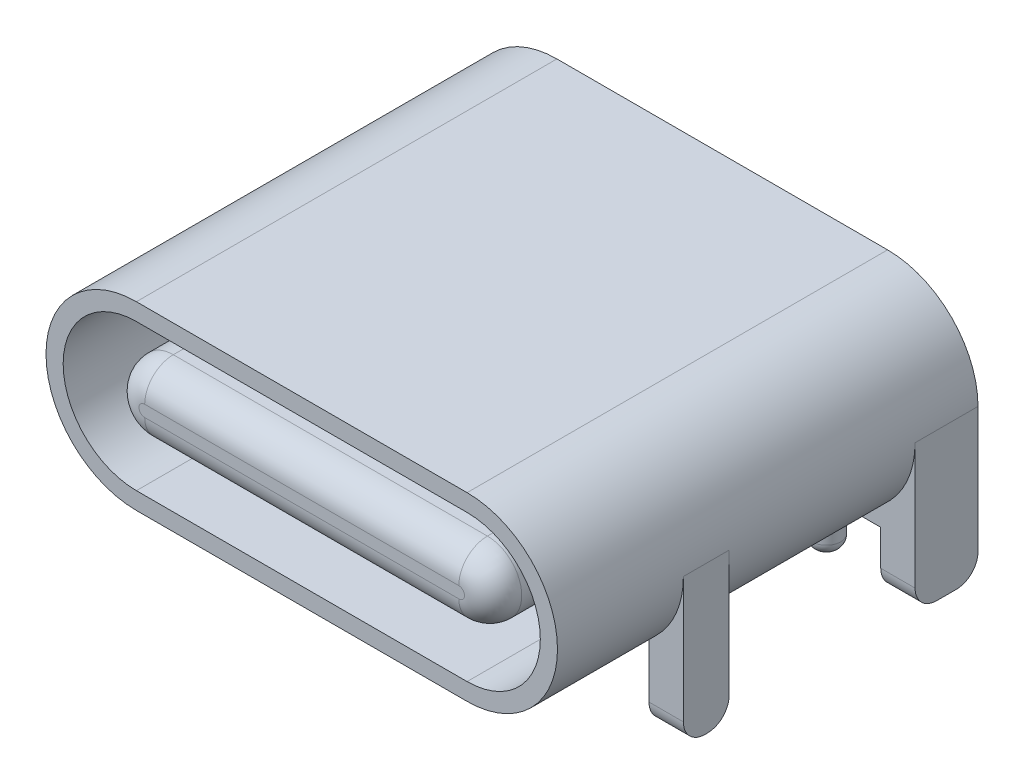
SolidWorks part; units mm, degrees
ref_plane "Front Plane" through (0, 0, 0) normal (0, 0, 1) x (1, 0, 0)
ref_plane "Top Plane" through (0, 0, 0) normal (0, 1, 0) x (1, 0, 0)
ref_plane "Right Plane" through (0, 0, 0) normal (1, 0, 0) x (0, 0, -1)
sketch "Sketch1" plane through (0, 0, 0) normal (0, 1, 0) x (1, 0, 0)
  line L1 (-4.47, 3.675) -> (4.47, 3.675)
  line L2 (-4.47, 3.675) -> (-4.47, -3.675)
  line L3 (-4.47, -3.675) -> (4.47, -3.675)
  line L4 (4.47, 3.675) -> (4.47, -3.675)
  line L5 (-4.47, 3.675) -> (4.47, -3.675) construction
  line L6 (-4.47, -3.675) -> (4.47, 3.675) construction
  point P0 (0, 0)
  point P5 (-1.9738, 5.526)
  dimension "D1" = 8.94
  dimension "D2" = 7.35
extrude "Boss-Extrude1" add sketch "Sketch1" along normal blind 3.16
sketch "Sketch2" plane through (0, 0, 3.675) normal (0, 0, 1) x (1, 0, 0)
  line L0 (0, 3.16) -> (0, 0) construction
  line L1 (-4.47, 3.16) -> (4.47, 3.16) construction
  line L2 (-2.89, 1.58) -> (-2.89, 3.16)
  line L7 (-4.47, 0) -> (4.47, 3.16) construction
  line L8 (-4.741, 1.58) -> (4.741, 1.58) construction
  line L9 (-2.89, 1.58) -> (-2.89, 0)
  line L10 (2.89, 1.58) -> (2.89, 3.16)
  line L11 (2.89, 1.58) -> (2.89, 0)
  line L12 (-2.89, 3.16) -> (2.89, 3.16)
  line L13 (-2.89, 0) -> (2.89, 0)
  line L15 (-3.345, 2.18) -> (3.345, 2.18)
  line L16 (-3.345, 2.18) -> (-3.345, 0.98)
  line L17 (-3.345, 0.98) -> (3.345, 0.98)
  line L18 (3.345, 2.18) -> (3.345, 0.98)
  line L19 (-3.345, 2.18) -> (3.345, 0.98) construction
  line L20 (-3.345, 0.98) -> (3.345, 2.18) construction
  line L21 (-4.47, 3.16) -> (4.47, 3.16)
  line L22 (-4.47, 3.16) -> (-4.47, 0)
  line L23 (-4.47, 0) -> (4.47, 0)
  line L24 (4.47, 3.16) -> (4.47, 0)
  line L25 (-4.47, 3.16) -> (4.47, 0) construction
  line L26 (-4.47, 0) -> (4.47, 3.16) construction
  circle A0 centre (-2.89, 1.58) radius 1.58
  circle A1 centre (2.89, 1.58) radius 1.58
  circle A2 centre (-2.745, 1.58) radius 0.6
  circle A3 centre (2.745, 1.58) radius 0.6
  point P5 (0, 1.58)
  point P10 (0, 1.58)
  point P24 (0, 1.58)
  line M12 (-4.47, 0) -> (4.47, 0)
  line M13 (4.47, 0) -> (4.47, 3.16)
  line M14 (4.47, 3.16) -> (-4.47, 3.16)
  line M15 (-4.47, 3.16) -> (-4.47, 0)
  dimension "D1" = 6.69
  dimension "D2" = 0
  dimension "D3" = 1.2
extrude "Cut-Extrude1" cut sketch "Sketch2" against normal blind 2.2 contours A0 M14 M15 | A0 L22 M12 | A1 M12 M13 | A1 L24 M14 region at (-4.1171, 2.8071, 3.675) region at (-4.1171, 0.3529, 3.675) region at (4.1171, 2.8071, 3.675) region at (4.1171, 0.3529, 3.675)
sketch "Sketch4" plane through (0, 0, 1.475) normal (0, 0, 1) x (1, 0, 0)
  line L1 (-4.47, 3.16) -> (4.47, 3.16)
  line L2 (-4.47, 3.16) -> (-4.47, 0)
  line L3 (-4.47, 0) -> (4.47, 0)
  line L4 (4.47, 3.16) -> (4.47, 0)
  line L5 (-4.47, 3.16) -> (4.47, 0) construction
  line L6 (-4.47, 0) -> (4.47, 3.16) construction
  circle A0 centre (-2.89, 1.58) radius 1.58
  circle A1 centre (2.89, 1.58) radius 1.58
  point P0 (0, 1.58)
  arc M1 (-4.47, 1.58) -> (-2.89, 3.16) centre (-2.89, 1.58) cw
  line M2 (-2.89, 3.16) -> (-4.47, 3.16)
  line M3 (-4.47, 3.16) -> (-4.47, 1.58)
extrude "Cut-Extrude2" cut sketch "Sketch4" against normal blind 0.8 contours M3 M1 M2 | A1 L4 L1 region at (-4.1171, 2.8071, 1.475) region at (4.1171, 2.8071, 1.475)
sketch "Sketch5" plane through (0, 0, -3.675) normal (0, 0, -1) x (-1, 0, 0)
  line L0 (0, 3.16) -> (0, 0) construction
  line L1 (-4.47, 3.16) -> (4.47, 3.16) construction
  line L3 (-4.47, 3.16) -> (4.47, 3.16)
  line L4 (-4.47, 3.16) -> (-4.47, 0)
  line L5 (-4.47, 0) -> (4.47, 0)
  line L6 (4.47, 3.16) -> (4.47, 0)
  line L7 (-4.47, 3.16) -> (4.47, 0) construction
  line L8 (-4.47, 0) -> (4.47, 3.16) construction
  circle A0 centre (-2.89, 1.58) radius 1.58
  circle A1 centre (2.89, 1.58) radius 1.58
  point P5 (0, 1.58)
  line M1 (-4.47, 0) -> (4.47, 0)
  line M2 (4.47, 0) -> (4.47, 3.16)
  line M3 (4.47, 3.16) -> (-4.47, 3.16)
  line M4 (-4.47, 3.16) -> (-4.47, 0)
extrude "Cut-Extrude3" cut sketch "Sketch5" against normal blind 3.25 from offset 1.1 contours A0 L3 M4 | A1 L6 M3 | A0 L4 M1 | A1 M1 M2 region at (4.1171, 2.8071, -3.675) region at (4.1171, 0.3529, -3.675) region at (-4.1171, 2.8071, -3.675) region at (-4.1171, 0.3529, -3.675) offset against normal yes
sketch "Sketch6" plane through (0, 0, -3.675) normal (0, 0, -1) x (-1, 0, 0)
  line L1 (-4.47, 3.16) -> (4.47, 3.16)
  line L2 (-4.47, 3.16) -> (-4.47, 0)
  line L3 (-4.47, 0) -> (4.47, 0)
  line L4 (4.47, 3.16) -> (4.47, 0)
  line L5 (-4.47, 3.16) -> (4.47, 0) construction
  line L6 (-4.47, 0) -> (4.47, 3.16) construction
  circle A0 centre (-2.89, 1.58) radius 1.58
  circle A1 centre (2.89, 1.58) radius 1.58
  point P0 (0, 1.58)
  line M3 (4.47, 3.16) -> (-4.47, 3.16)
  line M4 (-4.47, 3.16) -> (-4.47, 0)
extrude "Cut-Extrude4" cut sketch "Sketch6" against normal blind 3.25 contours A0 L1 M4 | A1 L4 M3 region at (4.1171, 2.8071, -3.675) region at (-4.1171, 2.8071, -3.675)
sketch "Sketch7" plane through (0, 0, 3.675) normal (0, 0, 1) x (1, 0, 0)
  line L0 (0, 3.16) -> (0, 0) construction
  line L1 (-2.89, 3.16) -> (2.89, 3.16) construction
  line L3 (-3.345, 2.18) -> (3.345, 2.18)
  line L4 (-3.345, 2.18) -> (-3.345, 0.98)
  line L5 (-3.345, 0.98) -> (3.345, 0.98)
  line L6 (3.345, 2.18) -> (3.345, 0.98)
  line L7 (-3.345, 2.18) -> (3.345, 0.98) construction
  line L8 (-3.345, 0.98) -> (3.345, 2.18) construction
  line L9 (-4.17, 2.86) -> (4.17, 2.86)
  line L10 (-4.17, 2.86) -> (-4.17, 0.3)
  line L11 (-4.17, 0.3) -> (4.17, 0.3)
  line L12 (4.17, 2.86) -> (4.17, 0.3)
  line L13 (-4.17, 2.86) -> (4.17, 0.3) construction
  line L14 (-4.17, 0.3) -> (4.17, 2.86) construction
  circle A0 centre (-2.745, 1.58) radius 0.6
  circle A1 centre (2.745, 1.58) radius 0.6
  circle A2 centre (-2.89, 1.58) radius 1.28
  circle A3 centre (2.89, 1.58) radius 1.28
  point P5 (0, 1.58)
  point P10 (0, 1.58)
  dimension "D1" = 6.69
  dimension "D2" = 1.2
  dimension "D3" = 8.34
  dimension "D4" = 2.56
extrude "Cut-Extrude5" cut sketch "Sketch7" against normal offset from surface (6.25 mm away) 1.1 contours L3 A2 L5 L4 | A0 L3 L4 | A0 L4 L5 | A1 L5 L6 | A3 L9 A2 L3 | A3 L5 A2 L11 | A1 L6 L3 | A3 L3 L6 L5 region at (-3.3802, 1.88, 3.675) region at (-3.211, 2.046, 3.675) region at (-3.211, 1.114, 3.675) region at (0, 2.5435, 3.675) region at (2.2484, 2.6468, 3.675) region at (0, 0.6165, 3.675) region at (3.211, 2.046, 3.675) region at (3.211, 1.114, 3.675) up to face at (0, 1.6891, -3.675)
fillet "Fillet1" radius 0.5 4 edges at (3.345, 1.58, 3.675) (0, 0.98, 3.675) (-3.345, 1.58, 3.675) (0, 2.18, 3.675)
sketch "Sketch8" plane through (0, 0, 1.475) normal (0, 0, 1) x (1, 0, 0)
  line L2 (-4.47, 0) -> (4.47, 0)
  line L3 (-4.47, 0) -> (-4.47, 1.58)
  line L4 (-4.47, 1.58) -> (4.47, 1.58)
  line L5 (4.47, 0) -> (4.47, 1.58)
  line L6 (-4.47, 1.58) -> (4.47, 1.58)
  line L7 (-4.47, 1.58) -> (-4.47, 3.16)
  line L8 (-4.47, 3.16) -> (4.47, 3.16)
  line L9 (4.47, 1.58) -> (4.47, 3.16)
  line L10 (-4.47, 0) -> (-3.87, 0)
  line L11 (-4.47, 0) -> (-4.47, 1.58)
  line L12 (-4.47, 1.58) -> (-3.87, 1.58)
  line L13 (-3.87, 0) -> (-3.87, 1.58)
  line L14 (4.47, 0) -> (3.87, 0)
  line L15 (4.47, 0) -> (4.47, 1.58)
  line L16 (4.47, 1.58) -> (3.87, 1.58)
  line L17 (3.87, 0) -> (3.87, 1.58)
  circle A0 centre (-2.89, 1.58) radius 1.58
  circle A1 centre (2.89, 1.58) radius 1.58
  arc M9 (4.47, 1.58) -> (2.89, 0) centre (2.89, 1.58) cw
  line M10 (2.89, 0) -> (4.47, 0)
  dimension "D1" = 0.6
  dimension "D2" = 0.6
extrude "Cut-Extrude6" cut sketch "Sketch8" against normal blind 1.1 contours A0 L13 L2 | L17 M10 M9 region at (-3.6306, 0.1, 1.475) region at (3.6306, 0.1, 1.475)
sketch "Sketch9" plane through (-4.47, 0, 0) normal (-1, 0, 0) x (0, 0, 1)
  line L1 (-3.675, 0) -> (-2.575, 0)
  line L2 (-3.675, 0) -> (-3.675, -0.62)
  line L3 (-3.295, -1) -> (-2.955, -1)
  line L4 (-2.575, 0) -> (-2.575, -0.62)
  line L5 (0.675, 0) -> (1.475, 0)
  line L6 (0.675, 0) -> (0.675, -0.62)
  line L7 (1.055, -1) -> (1.095, -1)
  line L8 (1.475, 0) -> (1.475, -0.62)
  arc A0 (1.095, -1) -> (1.475, -0.62) centre (1.095, -0.62) ccw
  arc A1 (1.055, -1) -> (0.675, -0.62) centre (1.055, -0.62) cw
  arc A2 (-2.955, -1) -> (-2.575, -0.62) centre (-2.955, -0.62) ccw
  arc A3 (-3.675, -0.62) -> (-3.295, -1) centre (-3.295, -0.62) ccw
  point P12 (1.475, -1)
  point P15 (0.675, -1)
  point P18 (-2.575, -1)
  point P21 (-3.675, -1)
  dimension "D5" = 0.38
  dimension "D1" = 1
  dimension "D2" = 1
  dimension "D3" = 1.1
  dimension "D4" = 0.8
extrude "Boss-Extrude2" add sketch "Sketch9" against normal blind 0.6
sketch "Sketch10" plane through (4.47, 0, 0) normal (1, 0, 0) x (0, 0, -1)
  line L1 (-1.475, 0) -> (-0.675, 0)
  line L2 (-1.475, 0) -> (-1.475, -0.62)
  line L3 (-1.095, -1) -> (-1.055, -1)
  line L4 (-0.675, 0) -> (-0.675, -0.62)
  line L5 (2.575, 0) -> (3.675, 0)
  line L6 (2.575, 0) -> (2.575, -0.62)
  line L7 (2.955, -1) -> (3.295, -1)
  line L8 (3.675, 0) -> (3.675, -0.62)
  arc A0 (3.295, -1) -> (3.675, -0.62) centre (3.295, -0.62) ccw
  arc A1 (2.955, -1) -> (2.575, -0.62) centre (2.955, -0.62) cw
  arc A2 (-0.675, -0.62) -> (-1.055, -1) centre (-1.055, -0.62) cw
  arc A3 (-1.095, -1) -> (-1.475, -0.62) centre (-1.095, -0.62) cw
  point P14 (2.575, -1)
  point P19 (-1.475, -1)
  dimension "D3" = 0.38
  dimension "D1" = 1
  dimension "D2" = 1
extrude "Boss-Extrude3" add sketch "Sketch10" against normal blind 0.6
sketch "Sketch11" plane through (0, 0, 0) normal (0, -1, 0) x (1, 0, 0)
  line L0 (0, 3.675) -> (0, -3.675) construction
  line L1 (-2.89, 3.675) -> (2.89, 3.675) construction
  line L2 (3.87, -3.675) -> (-3.87, -3.675) construction
  circle A0 centre (2.89, -2.605) radius 0.25
  circle A1 centre (-2.89, -2.605) radius 0.25
  dimension "D1" = 5.78
  dimension "D2" = 2.89
  dimension "D3" = 6.28
  dimension "D4" = 6.28
  dimension "D5" = 0.5
  dimension "D6" = 0.5
extrude "Boss-Extrude4" add sketch "Sketch11" along normal blind 1.8 from offset 1 offset against normal yes
fillet "Fillet2" radius 0.2 2 edges at (-2.89, -0.8, -2.855) (2.89, -0.8, -2.855)
sketch "Sketch12" plane through (0, 0, 0) normal (0, -1, 0) x (1, 0, 0)
  line L0 (0, -3.675) -> (0, -5.7521) construction
  line L1 (3.87, -3.675) -> (-3.87, -3.675) construction
  line L2 (-3.425, -4.075) -> (-2.975, -4.075)
  line L3 (0.15, -3.675) -> (0.35, -3.675)
  line L4 (0.15, -3.675) -> (0.15, -4.075)
  line L5 (0.15, -4.075) -> (0.35, -4.075)
  line L6 (0.35, -3.675) -> (0.35, -4.075)
  line L7 (0.65, -3.675) -> (0.85, -3.675)
  line L8 (0.65, -3.675) -> (0.65, -4.075)
  line L9 (0.65, -4.075) -> (0.85, -4.075)
  line L10 (0.85, -3.675) -> (0.85, -4.075)
  line L11 (1.15, -3.675) -> (1.35, -3.675)
  line L12 (1.15, -3.675) -> (1.15, -4.075)
  line L13 (1.15, -4.075) -> (1.35, -4.075)
  line L14 (1.35, -3.675) -> (1.35, -4.075)
  line L15 (1.65, -3.675) -> (1.85, -3.675)
  line L16 (1.65, -3.675) -> (1.65, -4.075)
  line L17 (1.65, -4.075) -> (1.85, -4.075)
  line L18 (1.85, -3.675) -> (1.85, -4.075)
  line L35 (2.625, -3.675) -> (2.175, -3.675)
  line L36 (2.625, -3.675) -> (2.625, -4.075)
  line L37 (2.625, -4.075) -> (2.175, -4.075)
  line L38 (2.175, -3.675) -> (2.175, -4.075)
  line L39 (3.425, -3.675) -> (2.975, -3.675)
  line L40 (3.425, -3.675) -> (3.425, -4.075)
  line L41 (3.425, -4.075) -> (2.975, -4.075)
  line L42 (2.975, -3.675) -> (2.975, -4.075)
  line L43 (-2.975, -3.675) -> (-2.975, -4.075)
  line L44 (-3.425, -3.675) -> (-2.975, -3.675)
  line L45 (-3.425, -3.675) -> (-3.425, -4.075)
  line L46 (-2.625, -4.075) -> (-2.175, -4.075)
  line L47 (-2.175, -3.675) -> (-2.175, -4.075)
  line L48 (-2.625, -3.675) -> (-2.175, -3.675)
  line L49 (-2.625, -3.675) -> (-2.625, -4.075)
  line L50 (-1.65, -4.075) -> (-1.85, -4.075)
  line L51 (-1.85, -3.675) -> (-1.85, -4.075)
  line L52 (-1.65, -3.675) -> (-1.85, -3.675)
  line L53 (-1.65, -3.675) -> (-1.65, -4.075)
  line L54 (-1.15, -4.075) -> (-1.35, -4.075)
  line L55 (-1.35, -3.675) -> (-1.35, -4.075)
  line L56 (-1.15, -3.675) -> (-1.35, -3.675)
  line L57 (-1.15, -3.675) -> (-1.15, -4.075)
  line L58 (-0.65, -4.075) -> (-0.85, -4.075)
  line L59 (-0.85, -3.675) -> (-0.85, -4.075)
  line L60 (-0.65, -3.675) -> (-0.85, -3.675)
  line L61 (-0.65, -3.675) -> (-0.65, -4.075)
  line L62 (-0.15, -4.075) -> (-0.35, -4.075)
  line L63 (-0.35, -3.675) -> (-0.35, -4.075)
  line L64 (-0.15, -3.675) -> (-0.35, -3.675)
  line L65 (-0.15, -3.675) -> (-0.15, -4.075)
  point P29 (0.75, -3.675)
  dimension "D1" = 0.2
  dimension "D2" = 0.2
  dimension "D3" = 0.2
  dimension "D4" = 0.2
  dimension "D5" = 0.45
  dimension "D6" = 0.45
  dimension "D7" = 2.175
  dimension "D8" = 0.15
  dimension "D9" = 0.65
  dimension "D10" = 1.15
  dimension "D11" = 1.65
  dimension "D12" = 2.975
  dimension "D13" = 0.4
  dimension "D14" = 0.4
  dimension "D15" = 0.4
  dimension "D16" = 0.4
  dimension "D17" = 0.4
  dimension "D18" = 0.4
extrude "Boss-Extrude5" add sketch "Sketch12" against normal blind 0.1
sketch "Sketch13" plane through (0, 0, 0) normal (0, -1, 0) x (1, 0, 0)
  line L1 (-3.425, -4.075) -> (3.425, -4.075)
  line L2 (-3.425, -4.075) -> (-3.425, -3.675)
  line L3 (-3.425, -3.675) -> (3.425, -3.675)
  line L4 (3.425, -4.075) -> (3.425, -3.675)
  line L5 (-3.425, -3.675) -> (-2.975, -3.675)
  line L6 (-3.425, -3.675) -> (-3.425, -4.075)
  line L7 (-3.425, -4.075) -> (-2.975, -4.075)
  line L8 (-2.975, -3.675) -> (-2.975, -4.075)
  line L9 (-2.625, -3.675) -> (-2.175, -3.675)
  line L10 (-2.625, -3.675) -> (-2.625, -4.075)
  line L11 (-2.625, -4.075) -> (-2.175, -4.075)
  line L12 (-2.175, -3.675) -> (-2.175, -4.075)
  line L13 (-1.85, -3.675) -> (-1.65, -3.675)
  line L14 (-1.85, -3.675) -> (-1.85, -4.075)
  line L15 (-1.85, -4.075) -> (-1.65, -4.075)
  line L16 (-1.65, -3.675) -> (-1.65, -4.075)
  line L17 (-1.35, -3.675) -> (-1.15, -3.675)
  line L18 (-1.35, -3.675) -> (-1.35, -4.075)
  line L19 (-1.35, -4.075) -> (-1.15, -4.075)
  line L20 (-1.15, -3.675) -> (-1.15, -4.075)
  line L21 (-0.85, -3.675) -> (-0.65, -3.675)
  line L22 (-0.85, -3.675) -> (-0.85, -4.075)
  line L23 (-0.85, -4.075) -> (-0.65, -4.075)
  line L24 (-0.65, -3.675) -> (-0.65, -4.075)
  line L25 (-0.35, -3.675) -> (-0.15, -3.675)
  line L26 (-0.35, -3.675) -> (-0.35, -4.075)
  line L27 (-0.35, -4.075) -> (-0.15, -4.075)
  line L28 (-0.15, -3.675) -> (-0.15, -4.075)
  line L29 (0.15, -3.675) -> (0.35, -3.675)
  line L30 (0.15, -3.675) -> (0.15, -4.075)
  line L31 (0.15, -4.075) -> (0.35, -4.075)
  line L32 (0.35, -3.675) -> (0.35, -4.075)
  line L33 (0.65, -3.675) -> (0.85, -3.675)
  line L34 (0.65, -3.675) -> (0.65, -4.075)
  line L35 (0.65, -4.075) -> (0.85, -4.075)
  line L36 (0.85, -3.675) -> (0.85, -4.075)
  line L37 (1.15, -3.675) -> (1.35, -3.675)
  line L38 (1.15, -3.675) -> (1.15, -4.075)
  line L39 (1.15, -4.075) -> (1.35, -4.075)
  line L40 (1.35, -3.675) -> (1.35, -4.075)
  line L41 (1.65, -3.675) -> (1.85, -3.675)
  line L42 (1.65, -3.675) -> (1.65, -4.075)
  line L43 (1.65, -4.075) -> (1.85, -4.075)
  line L44 (1.85, -3.675) -> (1.85, -4.075)
  line L45 (2.175, -3.675) -> (2.625, -3.675)
  line L46 (2.175, -3.675) -> (2.175, -4.075)
  line L47 (2.175, -4.075) -> (2.625, -4.075)
  line L48 (2.625, -3.675) -> (2.625, -4.075)
  line L49 (2.975, -3.675) -> (3.425, -3.675)
  line L50 (2.975, -3.675) -> (2.975, -4.075)
  line L51 (2.975, -4.075) -> (3.425, -4.075)
  line L52 (3.425, -3.675) -> (3.425, -4.075)
extrude "Boss-Extrude6" add sketch "Sketch13" along normal blind 0.05 contours L8 L3 L2 L1 | L12 L3 L10 L1 | L16 L3 L14 L1 | L20 L3 L18 L1 | L24 L3 L22 L1 | L28 L3 L26 L1 | L32 L3 L30 L1 | L36 L3 L34 L1 | L40 L3 L38 L1 | L44 L3 L42 L1 | L48 L3 L46 L1 | L3 L50 L1 L4 region at (-3.2, 0, -3.875) region at (-2.4, 0, -3.875) region at (-1.75, 0, -3.875) region at (-1.25, 0, -3.875) region at (-0.75, 0, -3.875) region at (-0.25, 0, -3.875) region at (0.25, 0, -3.875) region at (0.75, 0, -3.875) region at (1.25, 0, -3.875) region at (1.75, 0, -3.875) region at (2.4, 0, -3.875) region at (3.2, 0, -3.875)
